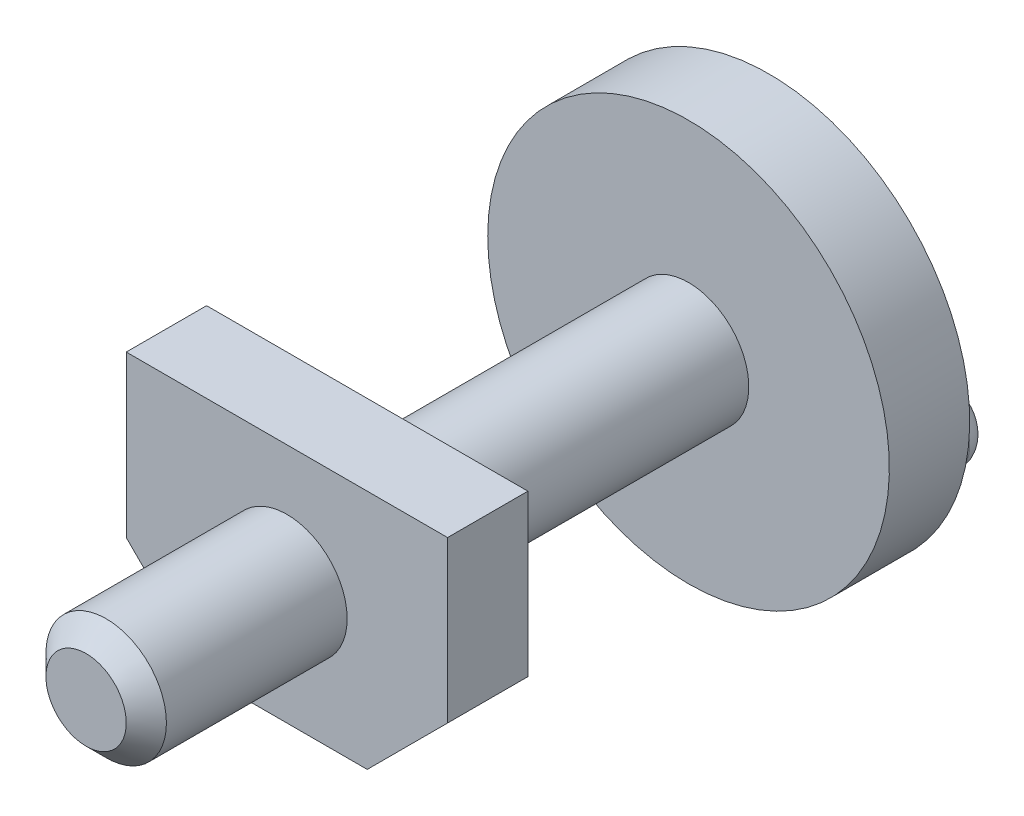
SolidWorks part; units mm, degrees
ref_plane "前视基准面" through (0, 0, 0) normal (0, 0, 1) x (1, 0, 0)
ref_plane "上视基准面" through (0, 0, 0) normal (0, 1, 0) x (1, 0, 0)
ref_plane "右视基准面" through (0, 0, 0) normal (1, 0, 0) x (0, 0, -1)
sketch "草图1" plane through (0, 0, 0) normal (0, 0, 1) x (1, 0, 0)
  circle A0 centre (0, 0) radius 15
  dimension "D1" = 30
extrude "凸台-拉伸1" add sketch "草图1" along normal blind 150
cosmetic thread "装饰螺纹线1" parameters "D2"=26.158
sketch "草图2" plane through (0, 0, 0) normal (0, 0, -1) x (-1, 0, 0)
  circle A0 centre (0, 0) radius 50
  dimension "D1" = 100
extrude "凸台-拉伸2" add sketch "草图2" along normal blind 20
sketch "草图3" plane through (0, 0, -20) normal (0, 0, -1) x (-1, 0, 0)
  circle A0 centre (0, 0) radius 42.5
  circle A1 centre (0, 0) radius 25
  dimension "D1" = 85
  dimension "D2" = 50
extrude "切除-拉伸1" cut sketch "草图3" against normal blind 5
chamfer "倒角1" distance 5 angle 45 2 edges at (-25, 0, -15) (-42.5, 0, -15)
sketch "草图4" plane through (0, 0, -20) normal (0, 0, -1) x (-1, 0, 0)
  line L0 (0, -50) -> (0, -42.5) construction
  circle A0 centre (0, 0) radius 50 construction
  circle A1 centre (0, 0) radius 42.5 construction
  circle A2 centre (0, -46.25) radius 3.75
extrude "凸台-拉伸3" add sketch "草图4" along normal blind 10
sketch "草图5" plane through (0, 0, -30) normal (0, 0, -1) x (-1, 0, 0)
  circle A0 centre (0, -46.25) radius 9
  dimension "D1" = 18
extrude "凸台-拉伸4" add sketch "草图5" along normal blind 36
fillet "圆角2" radius 5 1 edges at (-9, -46.25, -66)
chamfer "倒角2" distance 5 angle 45 1 edges at (-3.75, -46.25, -30)
chamfer "倒角3" distance 5 angle 45 1 edges at (15, 0, 150)
ref_plane "基准面1" through (0, 0, 80) normal (0, 0, 1) x (1, 0, 0)
sketch "草图6" plane through (0, 0, 80) normal (0, 0, 1) x (1, 0, 0)
  line L1 (-40, 30) -> (40, 30)
  line L2 (-40, 30) -> (-40, -30)
  line L3 (-40, -30) -> (40, -30)
  line L4 (40, 30) -> (40, -30)
  line L5 (-40, 30) -> (40, -30) construction
  line L6 (-40, -30) -> (40, 30) construction
  point P0 (0, 0)
  dimension "D1" = 60
  dimension "D2" = 80
extrude "凸台-拉伸5" add sketch "草图6" along normal blind 20
chamfer "倒角4" distance 20 angle 45 2 edges at (40, -30, 90) (-40, -30, 90)
equation "\"零件重量\"= \"SW-质量\""
